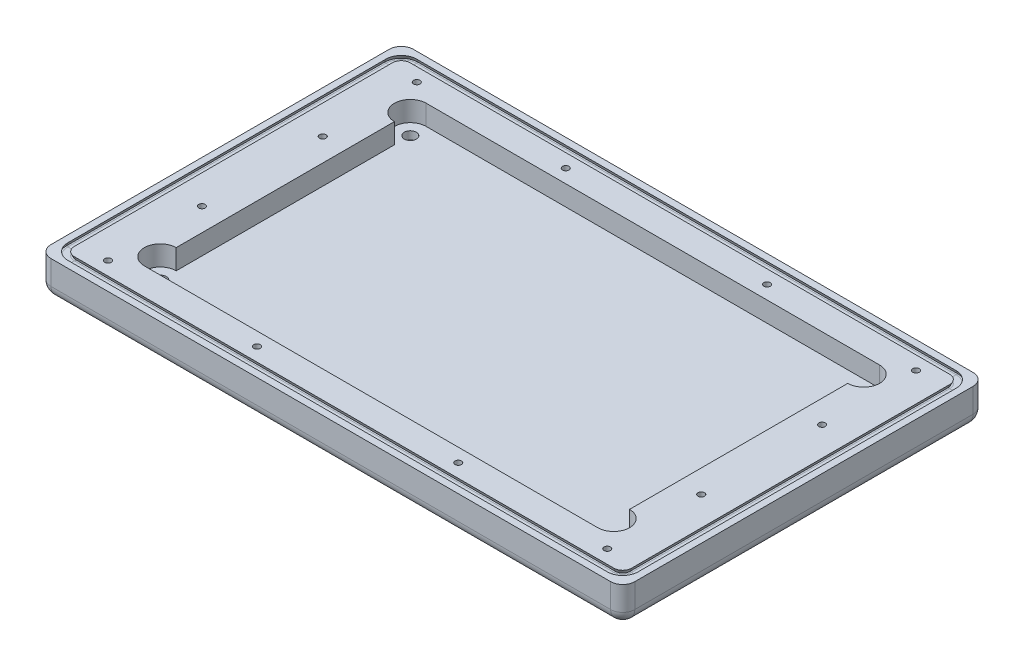
SolidWorks part; units mm, degrees
note: The reader was unsure of these and kept them because the rebuilt part matched: shared geometry of "Sketch5<4>".
ref_plane "Front Plane" through (0, 0, 0) normal (0, 0, 1) x (1, 0, 0)
ref_plane "Top Plane" through (0, 0, 0) normal (0, 1, 0) x (1, 0, 0)
ref_plane "Right Plane" through (0, 0, 0) normal (1, 0, 0) x (0, 0, -1)
sketch "Sketch1" plane through (0, 0, 0) normal (0, 1, 0) x (1, 0, 0)
  line L1 (0, 0) -> (145, 0)
  line L2 (0, 0) -> (0, 90)
  line L3 (0, 90) -> (145, 90)
  line L4 (145, 0) -> (145, 90)
  dimension "D1" = 145
  dimension "D2" = 90
extrude "Boss-Extrude1" add sketch "Sketch1" along normal blind 4
sketch "Sketch3" plane through (0, 4, 0) normal (0, 1, 0) x (1, 0, 0)
  line L4 (5, 85) -> (5, 5)
  line L5 (5, 5) -> (140, 5)
  line L6 (140, 5) -> (140, 85)
  line L7 (140, 85) -> (5, 85)
  line L8 (0, 90) -> (0, 0)
  line L9 (0, 0) -> (145, 0)
  line L10 (145, 0) -> (145, 90)
  line L11 (145, 90) -> (0, 90)
  line L12 (0, 90) -> (0, 0)
  line L13 (0, 0) -> (145, 0)
  line L14 (145, 0) -> (145, 90)
  line L15 (145, 90) -> (0, 90)
  dimension "D1" = 0
  dimension "D2" = 5
extrude "Boss-Extrude2" add sketch "Sketch3" along normal blind 5
sketch "Sketch5" plane through (0, 4, 0) normal (0, 1, 0) x (1, 0, 0)
  line L0 (72.5, 90) -> (72.5, 0)
  line L1 (145, 90) -> (0, 90) construction
  line L2 (0, 0) -> (145, 0) construction
  line L3 (0, 45) -> (145, 45)
  line L4 (0, 90) -> (0, 0) construction
  line L5 (145, 0) -> (145, 90) construction
  line L6 (16.2, 10) -> (128.8, 10)
  line L7 (16.2, 13.95) -> (128.8, 13.95)
  line L8 (16.2, 13.95) -> (16.2, 76.05)
  line L9 (16.2, 76.05) -> (128.8, 76.05)
  line L10 (128.8, 13.95) -> (128.8, 76.05)
  line L11 (16.2, 13.95) -> (128.8, 76.05) construction
  line L12 (16.2, 76.05) -> (128.8, 13.95) construction
  line L13 (16.2, 80) -> (128.8, 80)
  line L14 (128.8, 80) -> (128.8, 10) construction
  line L15 (5, 85) -> (140, 85)
  line L16 (5, 85) -> (5, 5)
  line L17 (5, 5) -> (140, 5)
  line L18 (140, 85) -> (140, 5)
  circle A0 centre (16.2, 76.05) radius 1.5
  circle A1 centre (128.8, 76.05) radius 1.5
  circle A2 centre (128.8, 13.95) radius 1.5
  circle A3 centre (16.2, 13.95) radius 1.5
  circle A4 centre (16.2, 13.95) radius 3.95
  circle A5 centre (16.2, 76.05) radius 3.95
  circle A6 centre (128.8, 13.95) radius 3.95
  circle A7 centre (128.8, 76.05) radius 3.95
  point P12 (72.5, 45)
  line M10 (140, 5) -> (140, 85)
  line M11 (140, 85) -> (5, 85)
  line M12 (5, 85) -> (5, 5)
  line M13 (5, 5) -> (140, 5)
  dimension "D3" = 3
  dimension "D4" = 3
  dimension "D5" = 3
  dimension "D6" = 3
  dimension "D7" = 7.9
  dimension "D8" = 7.9
  dimension "D9" = 7.9
  dimension "D10" = 7.9
  dimension "D1" = 112.6
  dimension "D2" = 62.1
extrude "Boss-Extrude4" add sketch "Sketch5<4>" along normal blind 5 contours A5 L13 L0 L3 L8 M11 M12 | A4 L8 L3 L0 L6 M12 M13 | A6 L6 L0 L3 L10 M13 M10 | A7 L10 L3 L0 L13 M10 M11
sketch "Sketch5<4>" plane through (0, 4, 0) normal (0, 1, 0) x (1, 0, 0) same geometry as "Sketch5"
sketch "Sketch6" plane through (0, 9, 0) normal (0, 1, 0) x (1, 0, 0)
  line L0 (0, 45) -> (145, 45) construction
  line L1 (0, 90) -> (0, 0) construction
  line L2 (145, 0) -> (145, 90) construction
  line L3 (72.5, 90) -> (72.5, 0) construction
  line L4 (145, 90) -> (0, 90) construction
  line L5 (0, 0) -> (145, 0) construction
  line L20 (142.5, 87.5) -> (2.5, 87.5)
  line L21 (2.5, 87.5) -> (2.5, 2.5)
  line L22 (2.5, 2.5) -> (142.5, 2.5)
  line L23 (142.5, 2.5) -> (142.5, 87.5)
  line L24 (139.5, 87.5) -> (5.5, 87.5)
  line L25 (2.5, 84.5) -> (2.5, 5.5)
  line L26 (5.5, 2.5) -> (139.5, 2.5)
  line L27 (142.5, 5.5) -> (142.5, 84.5)
  arc A6 (2.5, 5.5) -> (5.5, 2.5) centre (5.5, 5.5) ccw
  arc A7 (139.5, 2.5) -> (142.5, 5.5) centre (139.5, 5.5) ccw
  arc A8 (139.5, 87.5) -> (142.5, 84.5) centre (139.5, 84.5) cw
  arc A9 (5.5, 87.5) -> (2.5, 84.5) centre (5.5, 84.5) ccw
  dimension "D2" = 3
  dimension "D1" = 2.5
ref_plane "Plane for Gasket Groove" through (5.5, 0, 0) normal (1, 0, 0) x (0, 0, -1)
sketch "Sketch7" plane through (5.5, 0, 0) normal (1, 0, 0) x (0, 0, -1)
  line L0 (1.7, 9) -> (3.3, 9)
  line L3 (1.7, 8.1) -> (3.3, 8.1)
  line L4 (1.7, 8.1) -> (1.2993, 8.1)
  line L5 (1.2993, 8.1) -> (1.7, 9)
  line L6 (3.3, 8.1) -> (3.7007, 8.1)
  line L7 (3.7007, 8.1) -> (3.3, 9)
  dimension "D1" = 0.9
  dimension "D2" = 66
  dimension "D3" = 66
fillet "Fillet1" radius 3 4 edges at (145, 0, -45) (72.5, 0, -90) (72.5, 0, 0) (0, 0, -45)
fillet "Fillet3" radius 3 2 edges at (0, 6, -90) (0.8787, 0.8787, -89.1213)
fillet "Fillet4" radius 3 2 edges at (145, 6, -90) (144.1213, 0.8787, -89.1213)
fillet "Fillet5" radius 3 2 edges at (145, 6, 0) (144.1213, 0.8787, -0.8787)
fillet "Fillet6" radius 3 2 edges at (0, 6, 0) (0.8787, 0.8787, -0.8787)
sketch "Screw Hole Placement" plane through (0, 9, 0) normal (0, 1, 0) x (1, 0, 0)
  line L0 (72.5, 90) -> (72.5, 0) construction
  line L1 (142, 90) -> (3, 90) construction
  line L2 (3, 0) -> (142, 0) construction
  line L3 (0, 45) -> (145, 45) construction
  line L4 (0, 87) -> (0, 3) construction
  line L5 (145, 3) -> (145, 87) construction
  line L6 (8.5, 45) -> (5.5, 45)
  line L7 (5.5, -4.95) -> (5.5, 4.95) construction
  line L8 (10.5, 45) -> (10.5, 60) construction
  line L10 (16.2, 80) -> (128.8, 80) construction
  line L11 (72.5, 86.7) -> (66.8851, 86.7)
  line L12 (72.5, 86.7) -> (72.5, 80)
  line L13 (72.5, 80) -> (66.8851, 80)
  line L14 (66.8851, 86.7) -> (66.8851, 80)
  line L15 (66.8851, 83.35) -> (72.5, 83.35) construction
  line L16 (72.5, 83.35) -> (10.5, 83.35) construction
  line L17 (72.5, 83.35) -> (47.5, 83.35) construction
  line L18 (47.5, 83.35) -> (47.5, 92.6904) construction
  line L19 (72.5, 83.35) -> (51.5, 83.35) construction
  line L20 (51.5, 83.35) -> (51.5, 92.6904) construction
  circle A0 centre (10.5, 45) radius 2
  point P18 (72.5, 86.7)
  dimension "D2" = 4
  dimension "D1" = 3
  dimension "D3" = 15
  dimension "D4" = 62
  dimension "D5" = 25
  dimension "D6" = 21
ref_plane "Plane2" through (72.5, 0, 0) normal (1, 0, 0) x (0, 0, -1)
ref_plane "Plane3" through (0, 0, -45) normal (0, 0, 1) x (1, 0, 0)
sketch "Sketch10" plane through (0, 9, 0) normal (0, 1, 0) x (1, 0, 0)
  line L0 (66.8851, 86.7) -> (66.8851, 80) construction
  point P0 (10.5, 45)
  point P3 (10.5, 83.35)
  point P6 (47.5, 83.35)
  point P9 (51.5, 83.35)
  point P12 (66.8851, 83.35)
extrude "Cut-Extrude1" cut sketch "Sketch5" against normal blind 2 contours L7 A2 L10 | L10 A2 L7 | L10 A1 L9 | L9 A1 L10 | L9 A0 L8 | L8 A0 L9 | L7 A3 L8 | L8 A3 L7
sketch "Sketch11" plane through (0, 0, 0) normal (0, -1, 0) x (1, 0, 0)
  circle A0 centre (10.5, -83.35) radius 2.5
  circle A1 centre (47.5, -83.35) radius 2.5
  circle A3 centre (10.5, -60) radius 2.5
  dimension "D2" = 5
  dimension "D3" = 5
  dimension "D4" = 5
extrude "Cut-Extrude2" cut sketch "Sketch11" against normal blind 6
hole_wizard "M2x0.4 Tapped Hole1" positions "Sketch13" profile "Sketch14" tap size "M2x0.4" standard "ANSI Metric"
sketch "Sketch13" plane through (0, 0, 0) normal (0, -1, 0) x (-1, 0, 0)
  point P0 (-51.5, 83.35)
  point P3 (-47.5, 83.35)
  point P6 (-10.5, 83.35)
  point P9 (-10.5, 60)
  point P12 (-10.5, 45)
sketch "Sketch14" plane through (10.5, 0, -60) normal (1, 0, 0) x (0, 0, -1)
  line L0 (0, 0) -> (0, 9)
  line L1 (0, 9) -> (0.8, 9)
  line L2 (0.8, 9) -> (0.8, 0)
  line L5 (0.8, 0) -> (0, 0)
  line L11 (0, -6.35) -> (0, 107.95) construction
  dimension "Thru Tap Drill Dia." = 1.6
  dimension "Thru Tap Drill Depth" = 9
cosmetic thread "Hole Thread2" parameters "D2"=2
cosmetic thread "Hole Thread3" parameters "D2"=2
cosmetic thread "Hole Thread4" parameters "D2"=2
sweep "Cut-Sweep1" cut profiles "Sketch7" path "Sketch6"
mirror "Mirror4" about plane through (72.5, 0, 0) normal (1, 0, 0) of "M2x0.4 Tapped Hole1", "Cut-Extrude2"
cosmetic thread "Hole Thread26" parameters "D2"=2
cosmetic thread "Hole Thread27" parameters "D2"=2
cosmetic thread "Hole Thread28" parameters "D2"=2
mirror "Mirror5" about plane through (0, 0, -45) normal (0, 0, 1) of "Mirror4", "Cut-Extrude2", "M2x0.4 Tapped Hole1"
cosmetic thread "Hole Thread29" parameters "D2"=2
cosmetic thread "Hole Thread30" parameters "D2"=2
cosmetic thread "Hole Thread31" parameters "D2"=2
cosmetic thread "Hole Thread32" parameters "D2"=2
cosmetic thread "Hole Thread33" parameters "D2"=2
cosmetic thread "Hole Thread34" parameters "D2"=2
